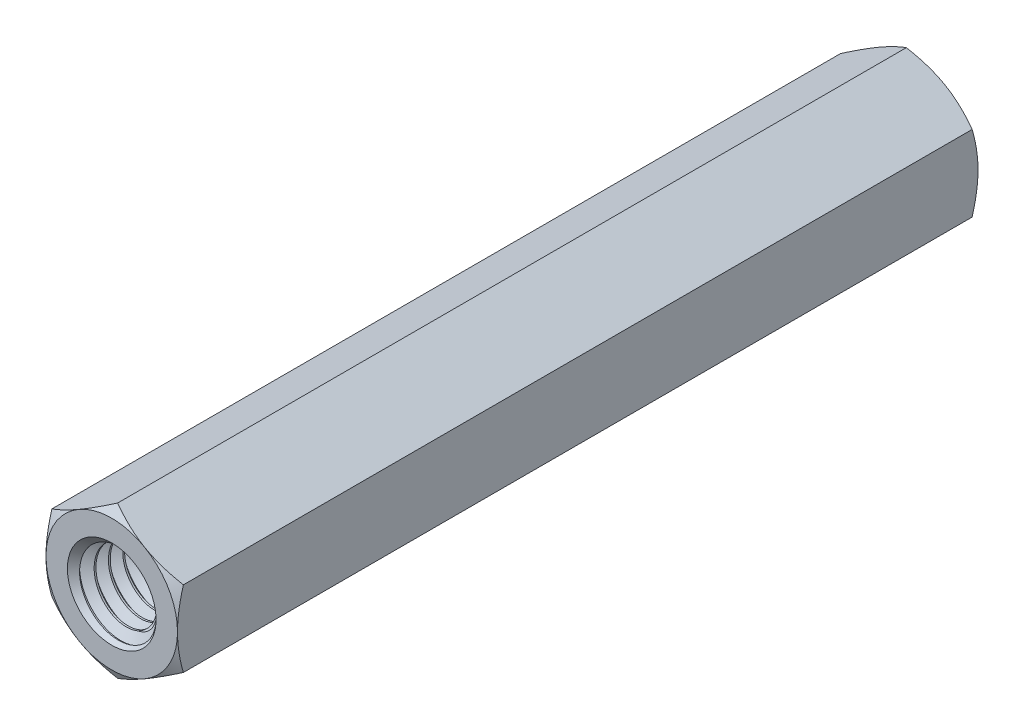
SolidWorks part; units mm, degrees
ref_plane "Front Plane" through (0, 0, 0) normal (0, 0, 1) x (1, 0, 0)
ref_plane "Top Plane" through (0, 0, 0) normal (0, 1, 0) x (1, 0, 0)
ref_plane "Right Plane" through (0, 0, 0) normal (1, 0, 0) x (0, 0, -1)
sketch "Sketch3" plane through (0, 0, 0) normal (1, 0, 0) x (0, 0, -1)
  line L0 (-14, 0) -> (14, 0) construction
  line L1 (0, 2.3) -> (0, -2.3) construction
  line L2 (-14, 1.5) -> (-14, -1.5) construction
  point P2 (8, 0)
  point P3 (-8, 0)
  dimension "Length" = 28
  dimension "Min Thread Length" = 6
  dimension "D1" = 6
  dimension "Thread Dia" = 3
  dimension "D2" = 4.6
sketch "Sketch1" plane through (0, 0, 0) normal (0, 0, 1) x (1, 0, 0)
  line L1 (0, 2.6558) -> (-2.3, 1.3279)
  line L2 (-2.3, 1.3279) -> (-2.3, -1.3279)
  line L3 (-2.3, -1.3279) -> (0, -2.6558)
  line L4 (0, -2.6558) -> (2.3, -1.3279)
  line L5 (2.3, -1.3279) -> (2.3, 1.3279)
  line L6 (2.3, 1.3279) -> (0, 2.6558)
  circle A0 centre (0, 0) radius 2.3 construction
  circle A1 centre (0, 0) radius 1.5
extrude "Extrude1" add sketch "Sketch1" along normal up to vertex (14 mm away) and the other way up to vertex (14 mm away) up to point (0, 0, 14) other way up to point (0, 0, -14)
sketch "Sketch11" plane through (0, 0, -14) normal (0, 0, -1) x (-1, 0, 0)
  circle A0 centre (0, 0) radius 1.5 construction
  circle A1 centre (0, 0) radius 1.5
curve "Helix/Spiral1" pitch 0.5 height 28.5 radius 1.5 centre (0, 0, -14) axis (0, 0, 1) start towards (0, 1, 0) parameters "Pitch"=0.5
sketch "Sketch12" plane through (0, 0, 0) normal (1, 0, 0) x (0, 0, -1)
  line L0 (14.4375, 1.5) -> (14, 1.5)
  line L1 (14.4375, 1.5) -> (14.25, 1.1752)
  line L2 (14.25, 1.1752) -> (14.1875, 1.1752)
  line L3 (14.1875, 1.1752) -> (14, 1.5)
  line L4 (14.2188, 1.1752) -> (14.2188, 1.5) construction
  line L5 (14.3438, 1.3376) -> (14.0938, 1.3376) construction
  dimension "D1" = 0.0625
  dimension "D2" = 0.25
  dimension "D3" = 60
sweep "Sweep1" add profiles "Sketch12" path "Helix/Spiral1"
sketch "Sketch6" plane through (0, 0, -14) normal (0, 0, -1) x (-1, 0, 0)
  line L6 (0, 2.6558) -> (-2.3, 1.3279)
  line L7 (-2.3, 1.3279) -> (-2.3, -1.3279)
  line L8 (-2.3, -1.3279) -> (0, -2.6558)
  line L9 (0, -2.6558) -> (2.3, -1.3279)
  line L10 (2.3, -1.3279) -> (2.3, 1.3279)
  line L11 (2.3, 1.3279) -> (0, 2.6558)
  line L12 (0, 2.6558) -> (-2.3, 1.3279)
  line L13 (-2.3, 1.3279) -> (-2.3, -1.3279)
  line L14 (-2.3, -1.3279) -> (0, -2.6558)
  line L15 (0, -2.6558) -> (2.3, -1.3279)
  line L16 (2.3, -1.3279) -> (2.3, 1.3279)
  line L17 (2.3, 1.3279) -> (0, 2.6558)
  dimension "D1" = 0
extrude "Extrude2" cut sketch "Sketch6" along normal through all
sketch "Sketch7" plane through (0, 0, -14) normal (0, 0, -1) x (-1, 0, 0)
  circle A2 centre (0, 0) radius 1.5508
  circle A3 centre (0, 0) radius 1.5508
  dimension "D1" = 0.0508
extrude "Extrude3" cut sketch "Sketch7" against normal through all draft 43
sketch "Sketch8" plane through (0, 0, -14) normal (0, 0, -1) x (-1, 0, 0)
  circle A0 centre (0, 0) radius 2.3 construction
  circle A1 centre (0, 0) radius 2.3
extrude "Extrude4" cut sketch "Sketch8" against normal through all draft 60 flip side to cut
mirror "Mirror1" about plane through (0, 0, 0) normal (0, 0, 1) of "Extrude2", "Extrude3", "Extrude4"
sketch "Sketch9" plane through (0, 0, 0) normal (1, 0, 0) x (0, 0, -1)
  line L1 (-8, 1.5508) -> (8, 1.5508)
  line L2 (-8, 1.5508) -> (-8, 0)
  line L3 (-8, 0) -> (8, 0)
  line L4 (8, 1.5508) -> (8, 0)
  line L7 (-14, 0) -> (14, 0) construction
revolve "Revolve" add sketch "Sketch9" angle 360 about L0
sketch "Sketch10" plane through (0, 0, 0) normal (1, 0, 0) x (0, 0, -1)
  line L0 (14, 1.5) -> (8, 1.5)
  line L1 (-14, 1.5) -> (-8, 1.5)
  line L2 (8, 1.5) -> (8, -1.5)
  line L3 (-14, -1.5508) -> (-8, -1.5508)
  line L4 (-8, 1.5) -> (-8, -1.5508)
  line L5 (8, -1.5) -> (14, -1.5)
sketch "Sketch13" plane through (0, 0, 14) normal (0, 0, 1) x (1, 0, 0)
  line L0 (0, 0) -> (1.1752, 0) construction
  line L1 (0, 0) -> (0.831, 0.831) construction
  line L2 (0, 0) -> (0.831, -0.831) construction
  arc A0 (0.5013, -1.063) -> (1.1082, -0.3912) centre (0, 0) ccw construction
  arc A1 (-0.8234, -0.8386) -> (0, -1.1752) centre (0, 0) ccw construction
  dimension "D1" = 45
  dimension "D2" = 45
equation "\"D1@Sketch3\" = \"Min Thread Length@Sketch3\""
equation "\"D3@Helix/Spiral1\" = \"Length@Sketch3\"+\"Pitch@Helix/Spiral1\""
equation "\"D1@Sketch12\" = \"Pitch@Helix/Spiral1\"*.125"
equation "\"D2@Sketch12\" = \"Pitch@Helix/Spiral1\"*.5"
